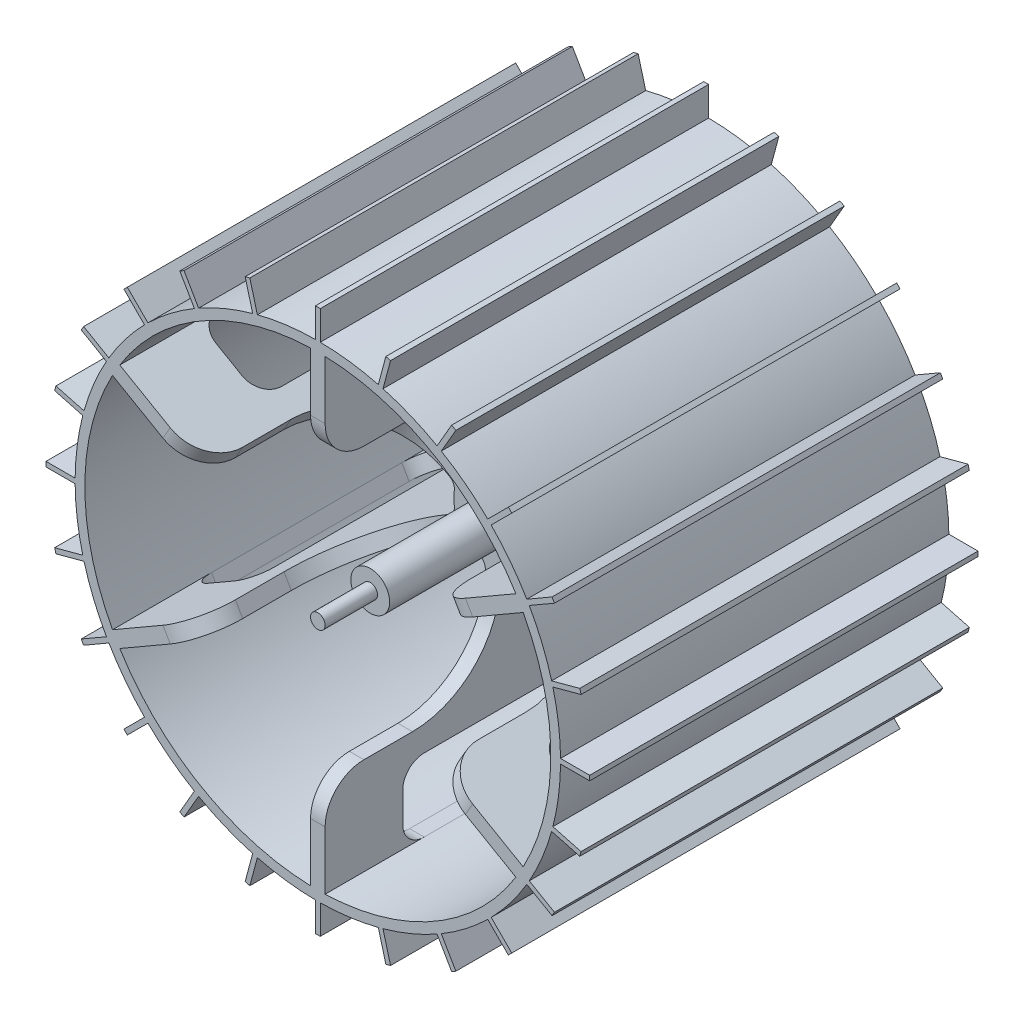
SolidWorks part; units mm, degrees
material "7075-O (SS)"
ref_plane "Front Plane" through (0, 0, 0) normal (0, 0, 1) x (1, 0, 0)
ref_plane "Top Plane" through (0, 0, 0) normal (0, 1, 0) x (1, 0, 0)
ref_plane "Right Plane" through (0, 0, 0) normal (1, 0, 0) x (0, 0, -1)
sketch "Sketch1" plane through (0, 0, 0) normal (0, 0, 1) x (1, 0, 0)
  circle A0 centre (0, 0) radius 250
  dimension "D1" = 500
extrude "Wheel Base" add sketch "Sketch1" along normal blind 400
ref_axis "Axis1" through (0, 0, 1218.9124) along (0, 0, -1)
sketch "Sketch3" plane through (0, 0, 0) normal (0, 1, 0) x (1, 0, 0)
  line L0 (0, 0) -> (0, -400) construction
  line L2 (2.5, -400) -> (-2.5, -400)
  line L3 (2.5, -400) -> (2.5, 0)
  line L4 (2.5, 0) -> (-2.5, 0)
  line L5 (-2.5, -400) -> (-2.5, 0)
  line L6 (2.5, -400) -> (-2.5, 0) construction
  line L7 (2.5, 0) -> (-2.5, -400) construction
  point P3 (0, -200)
  dimension "D1" = 400
  dimension "D2" = 400
  dimension "D3" = 5
extrude "Grouser" add sketch "Sketch3" along normal blind 280
pattern_circular "Grousers" count 24 over 360 about axis through (0, 0, 1218.9124) along (0, 0, -1) of "Grouser"
sketch "Sketch4" plane through (0, 0, 400) normal (0, 0, 1) x (1, 0, 0)
  circle A0 centre (0, 0) radius 40
  circle A1 centre (0, 0) radius 250
  circle A2 centre (0, 0) radius 240
  dimension "D1" = 10
  dimension "D2" = 80
extrude "Bore" cut sketch "Sketch4" against normal through all contours A2 A0 region at (-233.2118, 0, 400)
ref_plane "Midplane" through (0, 0, 200) normal (0, 0, 1) x (1, 0, 0)
sketch "Sketch5" plane through (0, 0, 200) normal (0, 0, 1) x (1, 0, 0)
  line L0 (0, 0) -> (0, 240) construction
  line L2 (-7.5, 0) -> (7.5, 0)
  line L3 (-7.5, 0) -> (-7.5, 240)
  line L4 (-7.5, 240) -> (7.5, 240)
  line L5 (7.5, 0) -> (7.5, 240)
  line L6 (-7.5, 0) -> (7.5, 240) construction
  line L7 (-7.5, 240) -> (7.5, 0) construction
  circle A0 centre (0, 0) radius 240 construction
  point P6 (0, 120)
  dimension "D1" = 15
extrude "Boss-Extrude1" add sketch "Sketch5" along normal mid plane 40 contours L2 L5 L4 L0 | L4 L3 L2 L0 region at (0, 120, 200)
sketch "Sketch7" plane through (0, 0, 200) normal (0, 0, 1) x (1, 0, 0)
  line L2 (-7.5, 239.8828) -> (-7.5, 39.2906)
  line L3 (-7.5, 139.8828) -> (7.5, 139.8828)
  line L4 (-7.5, 239.8828) -> (-7.5, 39.2906)
  line L8 (7.5, 39.2906) -> (7.5, 239.8828)
  line L11 (7.5, 139.8828) -> (7.5, 239.8828)
  arc A2 (7.5, 239.8828) -> (-7.5, 239.8828) centre (0, 0) ccw
  arc A3 (7.5, 239.8828) -> (-7.5, 239.8828) centre (0, 0) ccw
  arc A4 (7.5, 39.2906) -> (-7.5, 39.2906) centre (0, 0) ccw
  arc A5 (7.5, 39.2906) -> (-7.5, 39.2906) centre (0, 0) ccw
  dimension "D2" = 100
extrude "Boss-Extrude4" add sketch "Sketch7" along normal mid plane 400 contours L11 A3 L4 L3 region at (0, 189.9219, 200)
fillet "Fillet1" radius 90 2 edges at (0, 139.8828, 180) (0, 139.8828, 220)
fillet "Fillet2" radius 40 2 edges at (0, 139.8828, 0) (0, 139.8828, 400)
sketch "Sketch8" plane through (7.5, 0, 0) normal (1, 0, 0) x (0, 0, -1)
  line L0 (-200, 239.8828) -> (-200, 12.5296) construction
  line L1 (0, 239.8828) -> (-400, 239.8828) construction
  line L3 (-320, 164.8828) -> (-80, 164.8828)
  line L4 (-320, 164.8828) -> (-320, 239.8828)
  line L5 (-320, 239.8828) -> (-80, 239.8828)
  line L6 (-80, 164.8828) -> (-80, 239.8828)
  line L7 (-320, 164.8828) -> (-80, 239.8828) construction
  line L8 (-320, 239.8828) -> (-80, 164.8828) construction
  point P4 (-200, 202.3828)
  dimension "D3" = 240
  dimension "D1" = 75
extrude "Cut-Extrude2" cut sketch "Sketch8" against normal up to surface (15 mm away) up to face at (-7.5, 133.1766, 200)
fillet "Fillet3" radius 22 4 edges at (0, 164.8828, 80) (0, 164.8828, 320) (0, 239.8828, 320) (0, 239.8828, 80)
pattern_circular "CirPattern1" count 6 over 360 about axis through (0, 0, 1218.9124) along (0, 0, -1) of "Boss-Extrude1", "Fillet1", "Boss-Extrude4", "Fillet2", "Cut-Extrude2", "Fillet3"
sketch "Sketch9" plane through (0, 0, 0) normal (0, 0, -1) x (-1, 0, 0)
  circle A0 centre (0, 0) radius 40 construction
  circle A1 centre (0, 0) radius 40
extrude "Shorten Bore" cut sketch "Sketch9" against normal up to surface (180 mm away) up to face at (0, 44.764, 180)
sketch "Sketch10" plane through (0, 0, 400) normal (0, 0, 1) x (1, 0, 0)
  circle A0 centre (0, 0) radius 40
  circle A1 centre (0, 0) radius 40 construction
  circle A2 centre (0, 0) radius 20
  dimension "D1" = 40
extrude "Narrow Bore" cut sketch "Sketch10" against normal up to surface (180 mm away)
fillet "Fillet4" radius 10 12 edges at (37.7766, 13.1501, 200) (37.7766, -13.1501, 200) (-30.2766, 26.1405, 200) (30.2766, -26.1405, 200) (7.5, -39.2906, 200) (-7.5, -39.2906, 200) (-30.2766, -26.1405, 200) (-37.7766, -13.1501, 200) (-37.7766, 13.1501, 200) (-7.5, 39.2906, 200) (30.2766, 26.1405, 200) (7.5, 39.2906, 200)
sketch "Sketch11" plane through (0, 0, 400) normal (0, 0, 1) x (1, 0, 0)
  circle A0 centre (0, 0) radius 7.5
  circle A1 centre (0, 0) radius 20
  circle A2 centre (0, 0) radius 20 construction
  dimension "D1" = 15
extrude "Motor Shaft" cut sketch "Sketch11" against normal blind 54
ref_plane "Plane1" through (0, -280, 0) normal (0, -1, 0) x (-1, 0, 0)
equation "\"Wheel_Diameter\"= 50cm"
equation "\"D1@Sketch1\"=\"Wheel_Diameter\""
equation "\"Wheel_Width\"= 40cm"
equation "\"D1@Wheel Base\"=\"Wheel_Width\""
equation "\"D1@Sketch3\"=\"Wheel_Width\""
equation "\"D2@Sketch3\"=\"Wheel_Width\""
equation "\"Grouser_width\"= 5mm"
equation "\"D3@Sketch3\"=\"Grouser_width\""
equation "\"Grouser_height\"= 3cm"
equation "\"D1@Grouser\" = \"Wheel_Diameter\" / 2 + \"Grouser_height\""
equation "\"Number_of_Grousers\"= 24"
equation "\"D1@Grousers\" = \"Number_of_Grousers\""
equation "\"D1@Boss-Extrude4\"=\"Wheel_Width\""
equation "\"D2@Sketch7\"= \"Wheel_Diameter\" * .2"
equation "\"D1@Sketch8\" = \"Wheel_Diameter\" * .15"
equation "\"D3@Sketch8\"= \"Wheel_Width\" * .6"
